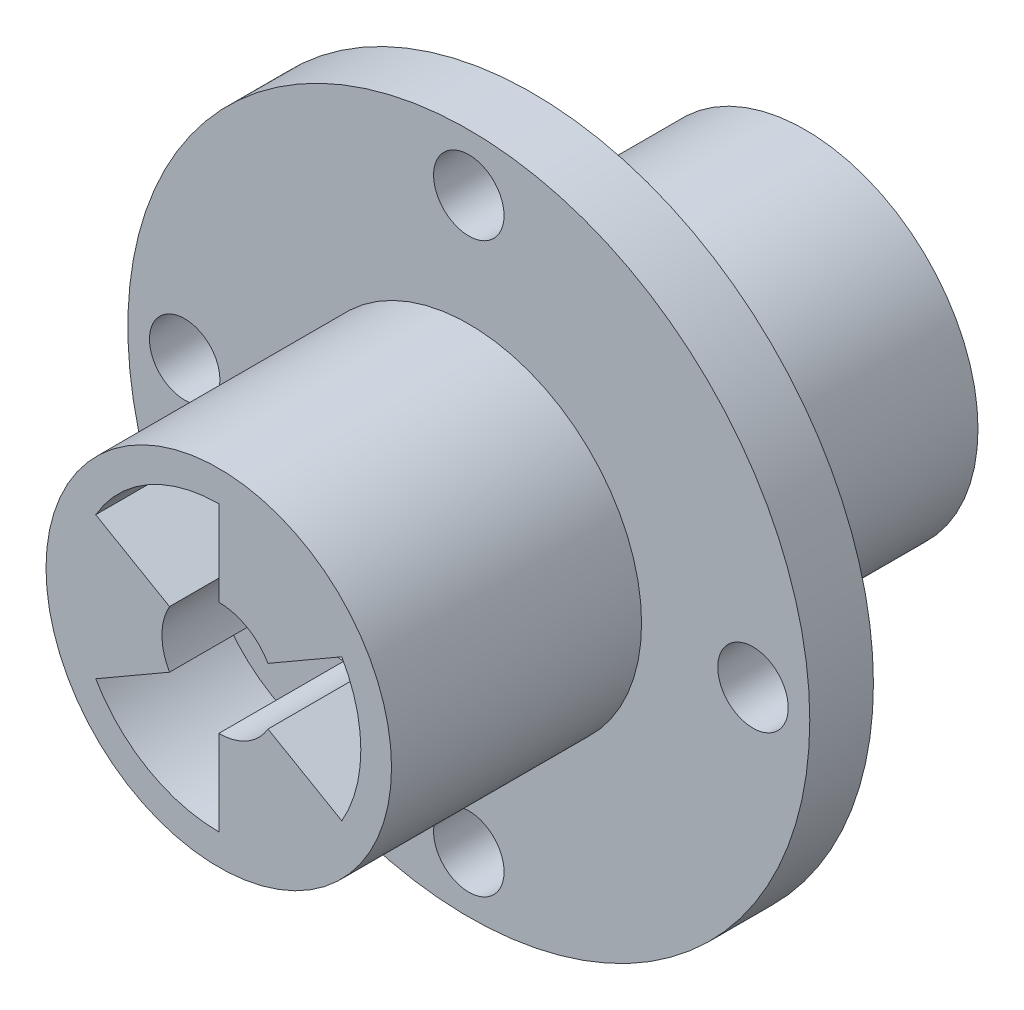
SolidWorks part; units mm, degrees
ref_plane "Front Plane" through (0, 0, 0) normal (0, 0, 1) x (1, 0, 0)
ref_plane "Top Plane" through (0, 0, 0) normal (0, 1, 0) x (1, 0, 0)
ref_plane "Right Plane" through (0, 0, 0) normal (1, 0, 0) x (0, 0, -1)
sketch "Sketch1" plane through (0, 0, 0) normal (0, 0, 1) x (1, 0, 0)
  circle A0 centre (0, 0) radius 12.5 construction
  circle A3 centre (0, 0) radius 15
  circle A4 centre (0, 12.5) radius 1.55
  circle A5 centre (12.5, 0) radius 1.55
  circle A6 centre (0, -12.5) radius 1.55
  circle A7 centre (-12.5, 0) radius 1.55
  point P15 (0, 0)
  dimension "D1" = 25
  dimension "D2" = 30
  dimension "D3" = 3.1
  dimension "D4" = 4
extrude "Boss-Extrude1" add sketch "Sketch1" along normal blind 2.8
sketch "Sketch3" plane through (0, 0, 0) normal (0, 0, 1) x (1, 0, 0)
  circle A0 centre (0, 0) radius 7.6
  dimension "D1" = 15.2
extrude "Boss-Extrude2" add sketch "Sketch3" along normal blind 11 from surface starting at face at (1.55, -12.5, 2.8)
sketch "Sketch4" plane through (0, 0, 13.8) normal (0, 0, 1) x (1, 0, 0)
  circle A0 centre (0, 0) radius 2.5
  dimension "D1" = 5
extrude "Cut-Extrude1" cut sketch "Sketch4" against normal through all both and the other way through all
sketch "Sketch5" plane through (0, 0, 13.8) normal (0, 0, 1) x (1, 0, 0)
  circle A0 centre (0, 0) radius 5
  dimension "D1" = 10
extrude "Cut-Extrude2" cut sketch "Sketch5" against normal blind 5.5
sketch "Sketch6" plane through (0, 0, 0) normal (0, 1, 0) x (1, 0, 0)
  line L0 (-7.6, -13.8) -> (7.6, -13.8) construction
  circle A0 centre (0, -11.3) radius 1.85
  dimension "D1" = 3.7
  dimension "D2" = 2.5
sketch "Sketch7" plane through (0, 0, 0) normal (0, 0, -1) x (-1, 0, 0)
  line L0 (1.85, 0) -> (-1.85, 0) construction
  circle A0 centre (0, 0) radius 7.6
  circle A1 centre (0, 0) radius 3.2
  dimension "D1" = 15.2
  dimension "D2" = 6.4
extrude "Boss-Extrude3" add sketch "Sketch7" along normal blind 12
sketch "Sketch8" plane through (0, 0, 0) normal (0, 0, -1) x (-1, 0, 0)
  circle A0 centre (0, 0) radius 3.2 construction
  circle A1 centre (0, 0) radius 3.2
  circle A2 centre (0, 0) radius 2.5
extrude "Boss-Extrude4" add sketch "Sketch8" along normal offset from surface (8 mm away) 4 up to face at (-7.6, 0, -12)
sketch "Sketch9" plane through (0, 0, 0) normal (0, 0, -1) x (-1, 0, 0)
  circle A0 centre (0, 0) radius 7.6 construction
  circle A1 centre (0, 0) radius 7.6
  circle A2 centre (0, 0) radius 8.25
  circle M2 centre (0, 0) radius 7.6
  dimension "D1" = 16.5
extrude "Boss-Extrude5" add sketch "Sketch9" along normal blind 3 contours A2 M2 region at (8.0167, 0, 0)
fillet "Fillet2" radius 1 1 edges at (8.25, 0, 0)
sketch "Sketch11" plane through (0, 0, 8.3) normal (0, 0, 1) x (1, 0, 0)
  circle A1 centre (0, 0) radius 5
  circle A2 centre (0, 0) radius 5
  circle M2 centre (0, 0) radius 5
  circle M3 centre (0, 0) radius 2.5
  dimension "D1" = 0
extrude "Boss-Extrude6" add sketch "Sketch11" along normal up to surface (5.5 mm away) contours M2 M3 region at (-4.8586, 0, 8.3) up to face at (5, 0, 13.8)
sketch "Sketch10" plane through (0, 0, 13.8) normal (0, 0, 1) x (1, 0, 0)
  line L0 (10.651, -6.1493) -> (-17.369, 10.028)
  line L1 (0, 12.2987) -> (0, -20.056)
  line L2 (-10.651, -6.1493) -> (17.369, 10.028)
  circle A0 centre (0, 0) radius 6.25
  point P0 (0, 0)
  point P12 (0, 0)
  circle M6 centre (0, 0) radius 2.5
  dimension "D1" = 12.5
  dimension "D2" = 3
extrude "Cut-Extrude3" cut sketch "Sketch10" against normal blind 5.5 contours L1 A0 L0 M6 | L2 A0 L1 M6 | L0 A0 L2 M6 region at (4.4336, 0, 13.8) region at (-2.2168, -3.8396, 13.8) region at (-2.2168, 3.8396, 13.8)
